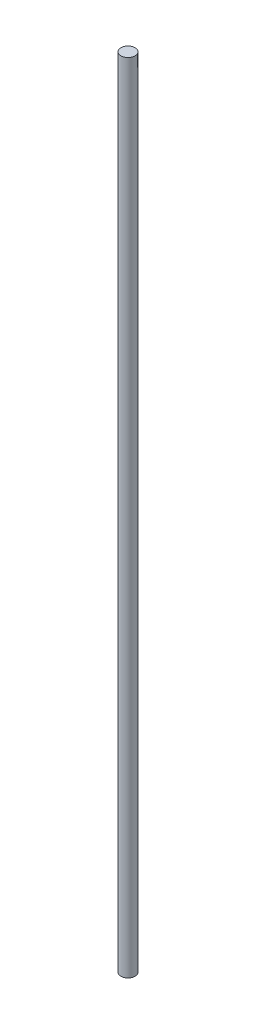
SolidWorks part; units mm, degrees
ref_plane "Plan de face" through (0, 0, 0) normal (0, 0, 1) x (1, 0, 0)
ref_plane "Plan de dessus" through (0, 0, 0) normal (0, 1, 0) x (1, 0, 0)
ref_plane "Plan de droite" through (0, 0, 0) normal (1, 0, 0) x (0, 0, -1)
sketch "Esquisse1" plane through (0, 0, 0) normal (0, 1, 0) x (1, 0, 0)
  circle A0 centre (0, 0) radius 2.5
  dimension "D1" = 5
sketch "Esquisse3" plane through (0, 0, 0) normal (0, 0, 1) x (1, 0, 0)
  line L0 (0, 0) -> (0, 282) construction
  line L5 (2.65, 282) -> (-2.65, 282) construction
extrude "Boss.-Extru.1" add sketch "Esquisse1" along direction (0, 1, 0) on the side of the normal up to vertex (282 mm away) up to point (0, 282, 0)
cosmetic thread "Représentation de filetage2" parameters "D2"=4.11
sketch "Esquisse2" plane through (0, 0, 0) normal (1, 0, 0) x (0, 0, -1)
  line L0 (1.5131, 280.1116) -> (1.5131, 283.8884)
  line L1 (1.5131, 283.8884) -> (-1.7577, 282)
  line L2 (-1.7577, 282) -> (1.5131, 280.1116)
  line L3 (-1.7577, 282) -> (1.5131, 282) construction
  line L4 (-2.4505, 282.4) -> (-2.4505, 281.6) construction
  line L5 (2.5, 282) -> (-2.5, 282) construction
  line L8 (0, 282) -> (0, 288.5862) construction
  dimension "D1" = 60
  dimension "D2" = 0.8
  dimension "D3" = 4.901
sketch "Esquisse4" plane through (0, 282, 0) normal (0, 1, 0) x (1, 0, 0)
  circle A0 centre (0, 0) radius 2.5
  circle A1 centre (0, 0) radius 2.5 construction
curve "Hélice/Spirale1" pitch 0.8 height 295 turns 368.75
sweep "Enlèvement de matière-Balayage1" [suppressed] cut profiles "Esquisse2" path "Hélice/Spirale1"
